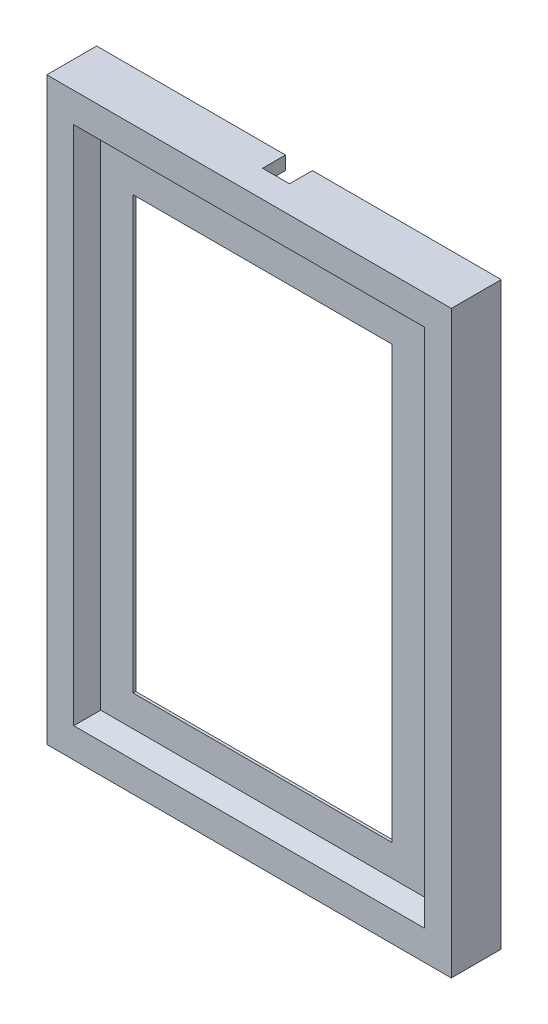
SolidWorks part; units mm, degrees
ref_plane "前视基准面" through (0, 0, 0) normal (0, 0, 1) x (1, 0, 0)
ref_plane "上视基准面" through (0, 0, 0) normal (0, 1, 0) x (1, 0, 0)
ref_plane "右视基准面" through (0, 0, 0) normal (1, 0, 0) x (0, 0, -1)
sketch "草图1" plane through (0, 0, 0) normal (0, 0, 1) x (1, 0, 0)
  line L1 (-75, 107.5) -> (75, 107.5)
  line L2 (-75, 107.5) -> (-75, -107.5)
  line L3 (-75, -107.5) -> (75, -107.5)
  line L4 (75, 107.5) -> (75, -107.5)
  line L5 (-75, 107.5) -> (75, -107.5) construction
  line L6 (-75, -107.5) -> (75, 107.5) construction
  line L7 (-48, 80) -> (48, 80)
  line L8 (-48, 80) -> (-48, -80)
  line L9 (-48, -80) -> (48, -80)
  line L10 (48, 80) -> (48, -80)
  line L11 (-48, 80) -> (48, -80) construction
  line L12 (-48, -80) -> (48, 80) construction
  point P0 (0, 0)
  point P6 (0, 0)
  dimension "D1" = 150
  dimension "D2" = 215
  dimension "D3" = 96
  dimension "D4" = 160
extrude "凸台-拉伸1" add sketch "草图1" along normal blind 15
sketch "草图2" plane through (0, 0, 15) normal (0, 0, 1) x (1, 0, 0)
  line L0 (75, 107.5) -> (-75, 107.5) construction
  line L1 (-60, 91.5) -> (60, 91.5)
  line L2 (-60, 91.5) -> (-60, -91.5)
  line L3 (-60, -91.5) -> (60, -91.5)
  line L4 (60, 91.5) -> (60, -91.5)
  line L5 (-60, 91.5) -> (60, -91.5) construction
  line L6 (-60, -91.5) -> (60, 91.5) construction
  line L7 (75, -107.5) -> (75, 107.5) construction
  point P0 (0, 0)
  dimension "D1" = 16
  dimension "D2" = 15
extrude "切除-拉伸1" cut sketch "草图2" against normal blind 5
chamfer "倒角1" distance 5 angle 45 4 edges at (0, -91.5, 15) (60, 0, 15) (-60, 0, 15) (0, 91.5, 15)
sketch "草图5" plane through (0, 0, 0) normal (0, 0, -1) x (-1, 0, 0)
  line L1 (-65, 95) -> (65, 95)
  line L2 (-65, 95) -> (-65, -95)
  line L3 (-65, -95) -> (65, -95)
  line L4 (65, 95) -> (65, -95)
  line L5 (-65, 95) -> (65, -95) construction
  line L6 (-65, -95) -> (65, 95) construction
  point P0 (0, 0)
  dimension "D1" = 190
  dimension "D2" = 130
extrude "切除-拉伸2" cut sketch "草图5" against normal blind 9
sketch "草图9" plane through (0, 0, 0) normal (0, 0, -1) x (-1, 0, 0)
  line L0 (65, -95) -> (65, 95) construction
  line L1 (-65, 102.5) -> (65, 102.5)
  line L2 (-65, 102.5) -> (-65, -102.5)
  line L3 (-65, -102.5) -> (65, -102.5)
  line L4 (65, 102.5) -> (65, -102.5)
  line L5 (-65, 102.5) -> (65, -102.5) construction
  line L6 (-65, -102.5) -> (65, 102.5) construction
  point P0 (0, 0)
  dimension "D1" = 205
extrude "切除-拉伸6" cut sketch "草图9" against normal blind 4
sketch "草图10" plane through (0, 0, 4) normal (0, 0, -1) x (-1, 0, 0)
  line L0 (-65, -102.5) -> (65, -102.5) construction
  line L1 (-61, 98.5) -> (61, 98.5) construction
  line L2 (-61, 98.5) -> (-61, -98.5) construction
  line L3 (-61, -98.5) -> (61, -98.5) construction
  line L4 (61, 98.5) -> (61, -98.5) construction
  line L5 (-61, 98.5) -> (61, -98.5) construction
  line L6 (-61, -98.5) -> (61, 98.5) construction
  line L7 (65, -102.5) -> (65, -95) construction
  circle A0 centre (61, 98.5) radius 2.5
  circle A1 centre (-61, 98.5) radius 2.5
  circle A2 centre (-61, -98.5) radius 2.5
  circle A3 centre (61, -98.5) radius 2.5
  point P0 (0, 0)
  dimension "5" = 5
  dimension "D1" = 4
  dimension "D2" = 4
extrude "切除-拉伸7" cut sketch "草图10" against normal blind 6
sketch "草图11" plane through (0, 0, 0) normal (0, 0, -1) x (-1, 0, 0)
  line L0 (75, -107.5) -> (-75, -107.5) construction
  line L1 (-5, 107.5) -> (5, 107.5)
  line L2 (-5, 107.5) -> (-5, -107.5)
  line L3 (-5, -107.5) -> (5, -107.5)
  line L4 (5, 107.5) -> (5, -107.5)
  line L5 (-5, 107.5) -> (5, -107.5) construction
  line L6 (-5, -107.5) -> (5, 107.5) construction
  point P0 (0, 0)
  dimension "D1" = 10
extrude "切除-拉伸8" cut sketch "草图11" against normal blind 5
sketch "草图12" plane through (0, 0, 0) normal (0, 0, -1) x (-1, 0, 0)
  line L0 (-5, 107.5) -> (-75, 107.5)
  line L1 (-75, 107.5) -> (-75, -107.5)
  line L2 (-75, -107.5) -> (-5, -107.5)
  line L3 (-5, -107.5) -> (-5, -102.5)
  line L4 (-5, -102.5) -> (-65, -102.5)
  line L5 (-65, -102.5) -> (-65, 102.5)
  line L6 (-65, 102.5) -> (-5, 102.5)
  line L7 (-5, 102.5) -> (-5, 107.5)
  line L8 (5, -102.5) -> (5, -107.5)
  line L9 (5, -107.5) -> (75, -107.5)
  line L10 (75, -107.5) -> (75, 107.5)
  line L11 (75, 107.5) -> (5, 107.5)
  line L12 (5, 107.5) -> (5, 102.5)
  line L13 (5, 102.5) -> (65, 102.5)
  line L14 (65, 102.5) -> (65, -102.5)
  line L15 (65, -102.5) -> (5, -102.5)
extrude "凸台-拉伸2" add sketch "草图12" along normal blind 3.5
